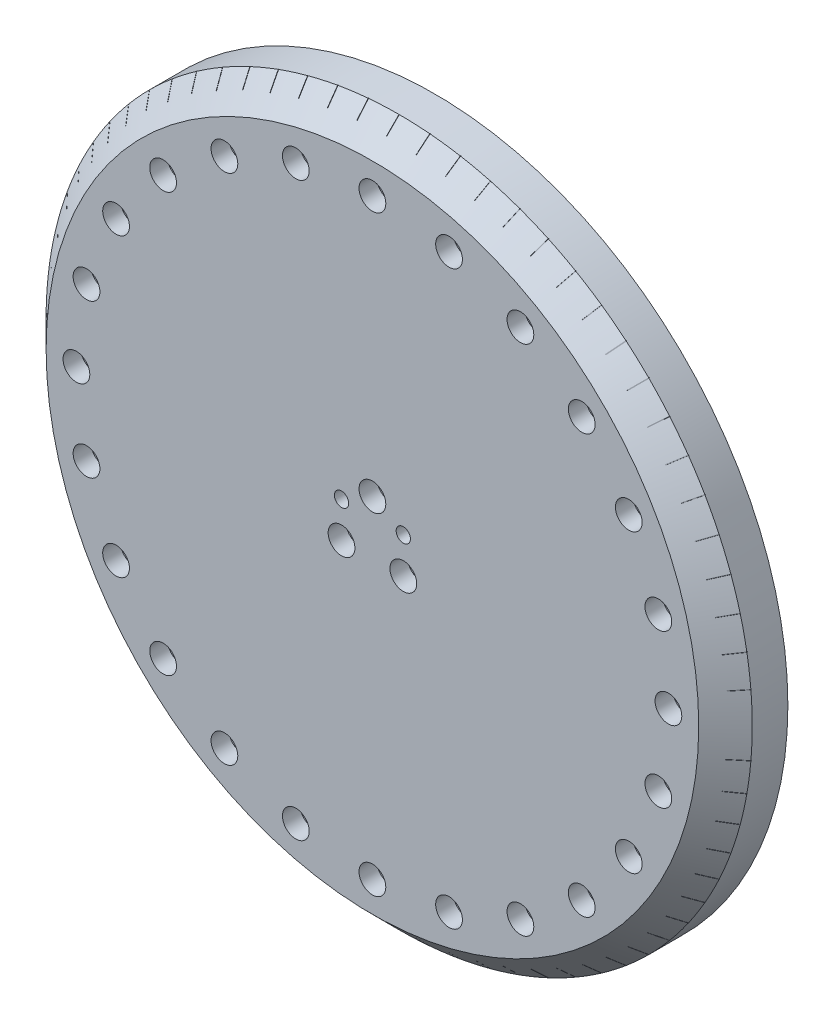
SolidWorks part; units mm, degrees
ref_plane "Plano frontal" through (0, 0, 0) normal (0, 0, 1) x (1, 0, 0)
ref_plane "Plano superior" through (0, 0, 0) normal (0, 1, 0) x (1, 0, 0)
ref_plane "Plano direito" through (0, 0, 0) normal (1, 0, 0) x (0, 0, -1)
sketch "Esboço1" plane through (0, 0, 0) normal (0, 0, 1) x (1, 0, 0)
  circle A0 centre (0, 235) radius 30 construction
  circle A1 centre (0, 235) radius 30 construction
  circle A2 centre (0, 235) radius 198
extrude "Ressalto-extrusão1" add sketch "Esboço1" along normal blind 35
chamfer "Chanfro1" distance 15 angle 45 1 edges at (198, 235, 35)
hole_wizard "Rebaixo para parafuso Allen sextavado de M81" positions "Esboço4" profile "Esboço5" counterbore size "M8" standard "DIN" end condition through all
sketch "Esboço4" plane through (0, 0, 35) normal (0, 0, 1) x (1, 0, 0)
  circle A0 centre (0, 235) radius 183 construction
  point P0 (0, 69)
  dimension "D1" = 166
sketch "Esboço5" plane through (0, 69, 35) normal (1, 0, 0) x (0, -1, 0)
  line L0 (0, 0) -> (0, 35)
  line L1 (0, 35) -> (4.5, 35)
  line L3 (4.5, 35) -> (4.5, 10)
  line L4 (4.5, 10) -> (7.5, 10)
  line L5 (7.5, 10) -> (7.5, 0)
  line L7 (7.5, 0) -> (0, 0)
  line L11 (0, -6.35) -> (0, 107.95) construction
  dimension "Thru Hole Dia." = 9
  dimension "Thru Hole Depth" = 35
  dimension "C'Bore Dia." = 15
  dimension "C'Bore Depth" = 10
ref_axis "Eixo1" through (0, 235, 20) along (0, 0, -1)
pattern_circular "PadrãoCircular1" count 24 over 360 about axis through (0, 235, 20) along (0, 0, -1) of "Rebaixo para parafuso Allen sextavado de M81"
sketch "Esboço7" plane through (0, 0, 0) normal (0, 0, -1) x (-1, 0, 0)
  circle A2 centre (0, 235.0391) radius 30
extrude "Corte-extrusão1" cut sketch "Esboço7" against normal blind 10
hole_wizard "Rebaixo para parafuso Allen sextavado de M82" positions "Esboço8" profile "Esboço9" counterbore size "M8" standard "DIN" end condition through all
sketch "Esboço8" plane through (0, 0, 35) normal (0, 0, 1) x (1, 0, 0)
  line L0 (0, 235) -> (-17.3205, 225) construction
  line L2 (0, 235) -> (17.3205, 225) construction
  line L4 (0, 255) -> (0, 235) construction
  circle A0 centre (0, 235) radius 20 construction
  point P0 (0, 255)
  point P2 (-17.3205, 225)
  point P4 (17.3205, 225)
  dimension "D1" = 40
  dimension "D2" = 120
  dimension "D3" = 120
sketch "Esboço9" plane through (0, 255, 35) normal (1, 0, 0) x (0, -1, 0)
  line L0 (0, 0) -> (0, 35)
  line L1 (0, 35) -> (4.5, 35)
  line L3 (4.5, 35) -> (4.5, 10)
  line L4 (4.5, 10) -> (7.5, 10)
  line L5 (7.5, 10) -> (7.5, 0)
  line L7 (7.5, 0) -> (0, 0)
  line L11 (0, -6.35) -> (0, 107.95) construction
  dimension "Thru Hole Dia." = 9
  dimension "Thru Hole Depth" = 35
  dimension "C'Bore Dia." = 15
  dimension "C'Bore Depth" = 10
hole_wizard "Furos-guia com Ø8.0mm1" positions "Esboço10" profile "Esboço11" hole size "Ø8.0" standard "DIN" end condition through all
sketch "Esboço10" plane through (0, 0, 35) normal (0, 0, 1) x (1, 0, 0)
  circle A0 centre (0, 235) radius 20 construction
  point P0 (-17.3205, 245)
  point P2 (17.3205, 245)
  dimension "D1" = 40
  dimension "D2" = 10
  dimension "D3" = 10
sketch "Esboço11" plane through (-17.3205, 245, 35) normal (1, 0, 0) x (0, -1, 0)
  line L0 (0, 0) -> (0, 35)
  line L1 (0, 35) -> (4, 35)
  line L2 (4, 35) -> (4, 0)
  line L5 (4, 0) -> (0, 0)
  line L11 (0, -6.35) -> (0, 107.95) construction
  dimension "Thru Hole Dia." = 8
  dimension "Thru Hole Depth" = 35
ref_plane "Plano1" through (0, 8.5, -8.5) normal (0, -0.7071, 0.7071) x (-1, 0, 0)
sketch "Esboço15" plane through (0, 8.5, -8.5) normal (0, -0.7071, 0.7071) x (-1, 0, 0)
  line L0 (0, 19.25) -> (0, -19.25) construction
  line L1 (0.1, -50.3051) -> (-0.1, -50.3051)
  line L2 (0.1, -50.3051) -> (0.1, -40.3051)
  line L4 (-0.1, -50.3051) -> (-0.1, -40.3051)
  line L5 (0.1, -40.3051) -> (0.1, -37.3051)
  line L6 (0.1, -37.3051) -> (-0.1, -37.3051)
  line L7 (-0.1, -37.3051) -> (-0.1, -40.3051)
  dimension "D1" = 10
  dimension "D2" = 0.2
  dimension "D3" = 0.1
  dimension "D4" = 3
extrude "Corte-extrusão2" cut sketch "Esboço15" against normal blind 0.2
pattern_circular "PadrãoCircular2" count 72 over 360 about axis through (0, 235, 20) along (0, 0, -1) of "Corte-extrusão2"
sketch "Esboço16" plane through (0, 8.5, -8.5) normal (0, -0.7071, 0.7071) x (-1, 0, 0)
  text T0 "0\r\n" font "Century Gothic" height 5
ref_plane "Plano2" through (109, 0, 109) normal (0.7071, 0, 0.7071) x (0.7071, 0, -0.7071)
sketch "Esboço18" plane through (109, 0, 109) normal (0.7071, 0, 0.7071) x (0.7071, 0, -0.7071)
  text T0 "90" font "Century Gothic" height 5
ref_plane "Plano3" through (-109, 0, 109) normal (-0.7071, 0, 0.7071) x (0.7071, 0, 0.7071)
sketch "Esboço19" plane through (-109, 0, 109) normal (-0.7071, 0, 0.7071) x (0.7071, 0, 0.7071)
  text T0 "-90" font "Century Gothic" height 5
ref_plane "Plano4" through (0, 226.5, 226.5) normal (0, 0.7071, 0.7071) x (1, 0, 0)
sketch "Esboço20" plane through (0, 226.5, 226.5) normal (0, 0.7071, 0.7071) x (1, 0, 0)
  text T0 "180" font "Century Gothic" height 5
